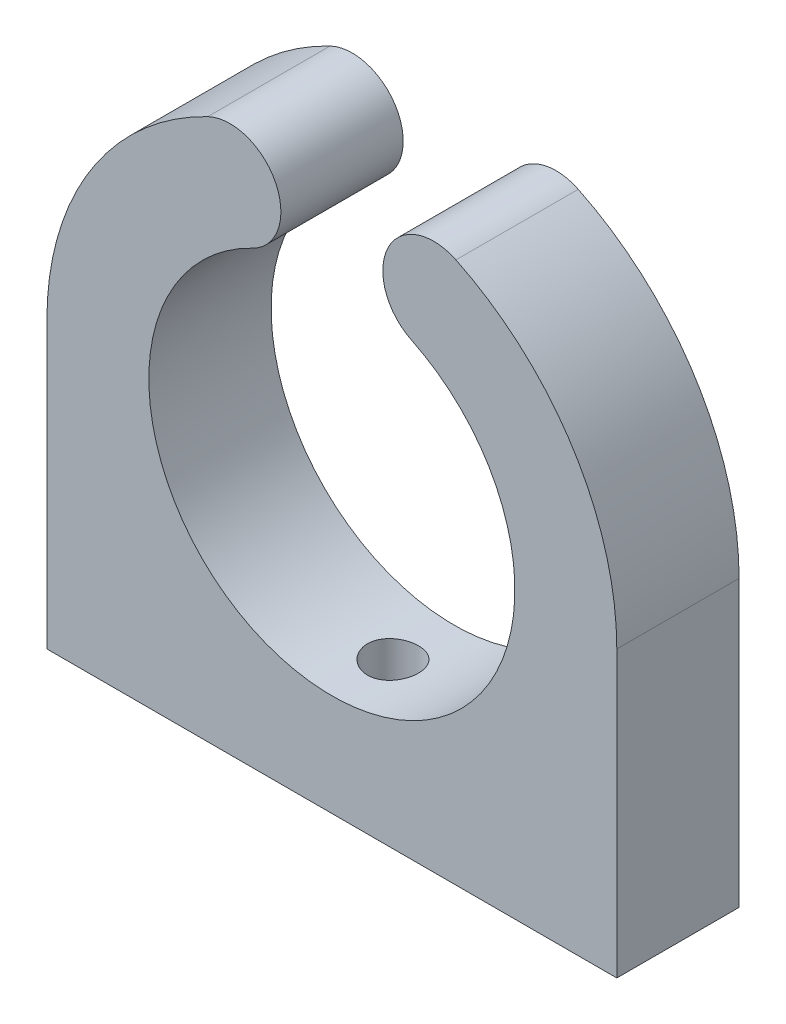
SolidWorks part; units mm, degrees
material "Thornel Mat VMA"
ref_plane "Front Plane" through (0, 0, 0) normal (0, 0, 1) x (1, 0, 0)
ref_plane "Top Plane" through (0, 0, 0) normal (0, 1, 0) x (1, 0, 0)
ref_plane "Right Plane" through (0, 0, 0) normal (1, 0, 0) x (0, 0, -1)
sketch "Sketch1" plane through (0, 0, 0) normal (0, 0, 1) x (1, 0, 0)
  line L0 (-13.98, -13.98) -> (13.98, -13.98)
  line L1 (13.98, -13.98) -> (13.98, 0)
  line L2 (-13.98, -13.98) -> (-13.98, 0)
  circle A0 centre (0, 0) radius 9 construction
  arc A1 (-8.98, 0) -> (3.9111, 8.0835) centre (0, 0) ccw
  arc A2 (13.98, 0) -> (6.0889, 12.5844) centre (0, 0) ccw
  arc A3 (-3.9111, 8.0835) -> (-6.0889, 12.5844) centre (-5, 10.3339) ccw
  circle A4 centre (0, 0) radius 13.98 construction
  circle A5 centre (0, 0) radius 8.98 construction
  arc A6 (6.0889, 12.5844) -> (3.9111, 8.0835) centre (5, 10.3339) ccw
  arc A7 (-3.9111, 8.0835) -> (-8.98, 0) centre (0, 0) ccw
  arc A8 (-6.0889, 12.5844) -> (-13.98, 0) centre (0, 0) ccw
  point P10 (0, -13.98)
  point P12 (-9.02, 0)
  point P13 (-8.9918, -0.3831)
  point P14 (-9, 0)
  point P17 (13.4074, 4.0991)
  point P22 (8.6259, 2.6372)
  point P26 (5.0796, 10.3396)
  dimension "D1" = 18
  dimension "D2" = 0.02
  dimension "D7" = 5
  dimension "D4" = 5
  dimension "D3" = 5
extrude "Boss-Extrude1" add sketch "Sketch1" along normal mid plane 6 contours L1 A2 L2 L0 A1 region at (-13.5926, -6.99, 0)
hole_wizard "M3x0.5 Tapped Hole1" positions "3DSketch2" profile "Sketch3" tap size "M3x0.5" standard "ANSI Metric"
sketch3d "3DSketch2"
  point P0 (0, -13.98, 0)
  point P3 (0, 0, 0)
sketch "Sketch3" plane through (0, -13.98, 0) normal (1, 0, 0) x (0, 0, -1)
  line L0 (0, 0) -> (0, 22.0635)
  line L1 (0, 22.0635) -> (1.25, 21.3124)
  line L2 (1.25, 21.3124) -> (1.25, 0.275)
  line L3 (1.25, 0.275) -> (1.525, 0)
  line L5 (1.525, 0) -> (0, 0)
  line L6 (-1.25, 0.275) -> (-1.525, 0) construction
  line L10 (0, 22.0635) -> (-1.25, 21.3124) construction
  line L11 (0, -6.35) -> (0, 107.95) construction
  dimension "Tap Drill Dia." = 2.5
  dimension "Tap Drill Depth" = 22.0635
  dimension "Near C'Sink Dia." = 3.05
  dimension "Near C'Sink Angle" = 90
  dimension "Drill Angle" = 118
cosmetic thread "Hole Thread1"
equation "\"diam\" = 18mm"
equation "\"width\" = 6"
equation "\"D1@Sketch1\"=\"diam\""
equation "\"tolerance\"= 0.02"
equation "\"D2@Sketch1\"=\"tolerance\""
equation "\"D1@Boss-Extrude1\"=\"width\""
